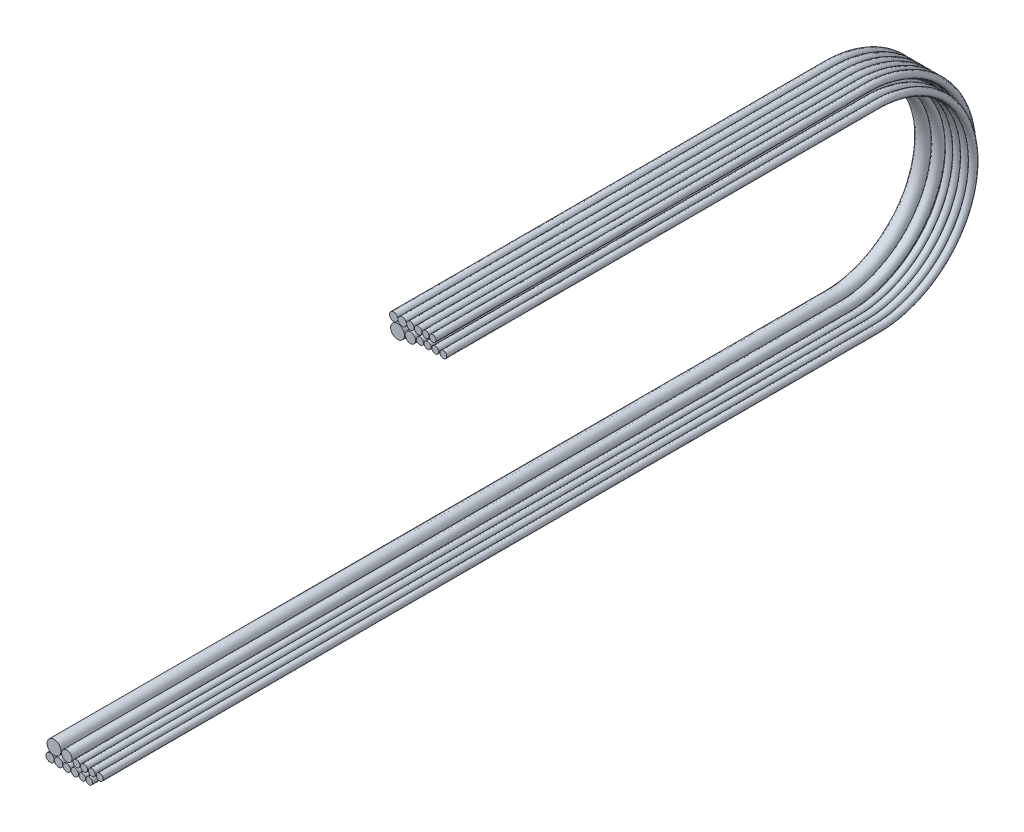
SolidWorks part; units mm, degrees
ref_plane "Front Plane" through (0, 0, 0) normal (0, 0, 1) x (1, 0, 0)
ref_plane "Top Plane" through (0, 0, 0) normal (0, 1, 0) x (1, 0, 0)
ref_plane "Right Plane" through (0, 0, 0) normal (1, 0, 0) x (0, 0, -1)
sketch "Sketch1" plane through (0, 0, 0) normal (0, 0, 1) x (1, 0, 0)
  line L1 (18.5, 18) -> (-18.5, 18) construction
  line L2 (18.5, 18) -> (18.5, 0) construction
  line L3 (18.5, 0) -> (-18.5, 0) construction
  line L4 (-18.5, 18) -> (-18.5, 0) construction
  circle A0 centre (-16.1, 2.4) radius 2.4
  circle A1 centre (-11.18, 2.4) radius 2.4
  circle A2 centre (-6.4473, 2.15) radius 2.15
  circle A3 centre (-1.9096, 2.15) radius 2.15
  circle A4 centre (2.4561, 1.95) radius 1.95
  circle A5 centre (6.4782, 1.95) radius 1.95
  circle A6 centre (-0.8441, 6.9864) radius 2
  circle A7 centre (-13.8535, 8.6823) radius 4
  circle A8 centre (-6.4473, 8.0498) radius 3
  circle A9 centre (3.5072, 6.9864) radius 2
  circle A10 centre (8.0021, 6.9864) radius 2
  circle A11 centre (12.5926, 6.9864) radius 2
  dimension "D3" = 4.8
  dimension "D4" = 4.3
  dimension "D5" = 3.9
  dimension "D6" = 4
  dimension "D7" = 8
  dimension "D8" = 6
  dimension "D1" = 37
  dimension "D2" = 18
sketch "Sketch2" plane through (0, 0, 0) normal (1, 0, 0) x (0, 0, -1)
  spline S0 degree 3 poles (-999.9983, 9.7) (-516.8663, 9.7) (-33.6624, 9.7) (449.6135, 9.7) (449.8295, 9.7016) (449.9734, 9.7031) (450.0454, 9.7039) (554.4997, 10.969) (554.4997, 115.431) (450.0454, 116.6961) (449.9734, 116.6969) (449.8295, 116.6984) (449.6135, 116.7) (32.628, 116.7) (-384.2854, 116.7) (-801.1269, 116.7) knots -1.237296 -1.237296 -1.237296 -1.237296 0.556039 0.556306 0.556573 0.55684 0.55684 0.55684 0.689221 0.689221 0.689221 0.689489 0.689756 0.690023 2.237294 2.237294 2.237294 2.237294 weights 1 1 1 1 1 1 1 0.341407 0.341407 1 1 1 1 1 1 1 only from (0, 9.7) to (198.8702, 116.7) construction
  spline S1 degree 3 poles (0, 9.7) (149.7992, 9.7) (299.6703, 9.7) (449.6135, 9.7) (449.8295, 9.7016) (449.9734, 9.7031) (450.0454, 9.7039) (554.4997, 10.969) (554.4997, 115.431) (450.0454, 116.6961) (449.9734, 116.6969) (449.8295, 116.6984) (449.6135, 116.7) (365.9604, 116.7) (282.3793, 116.7) (198.8702, 116.7) knots 0 0 0 0 0.556039 0.556306 0.556573 0.55684 0.55684 0.55684 0.689221 0.689221 0.689221 0.689489 0.689756 0.690023 1 1 1 1 weights 1 1 1 1 1 1 1 0.341407 0.341407 1 1 1 1 1 1 1
sweep "Sweep1" add profiles "Sketch1" path "Sketch2"
